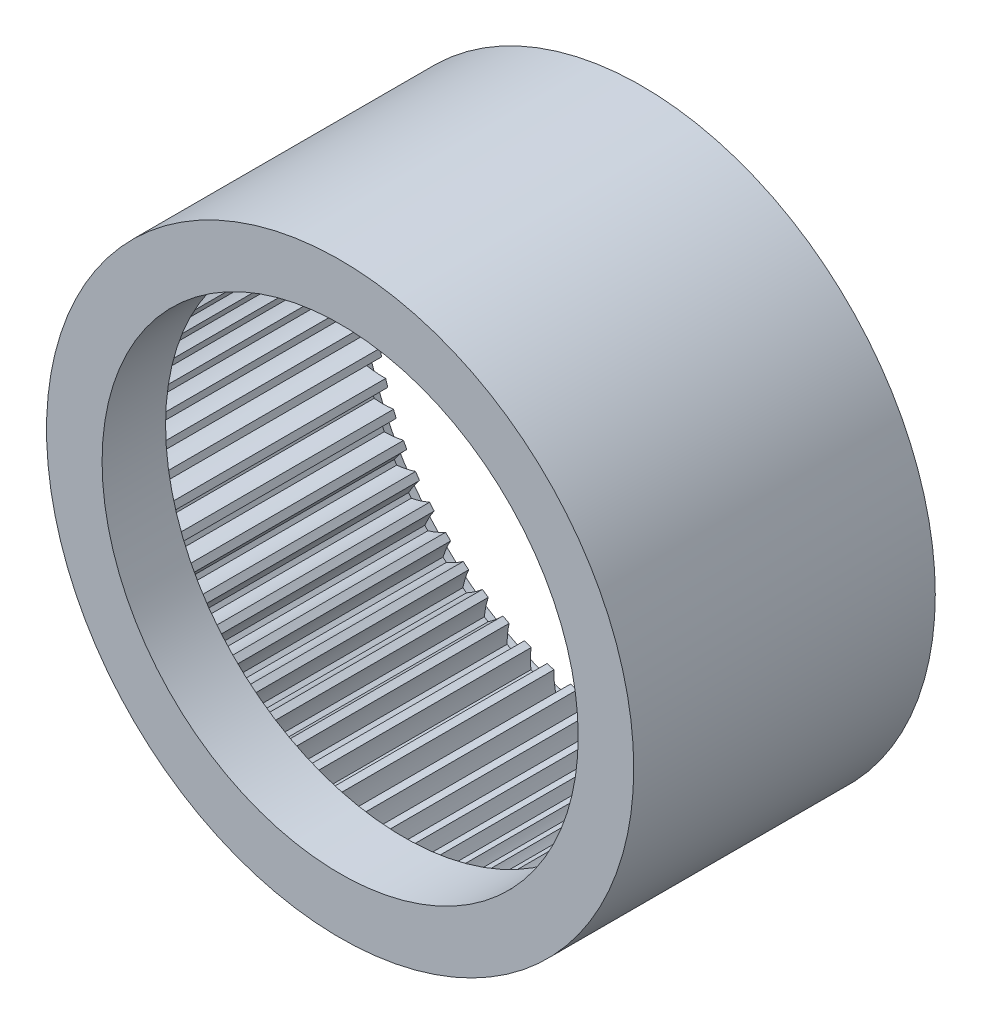
SolidWorks part; units mm, degrees
ref_plane "前视基准面" through (0, 0, 0) normal (0, 0, 1) x (1, 0, 0)
ref_plane "上视基准面" through (0, 0, 0) normal (0, 1, 0) x (1, 0, 0)
ref_plane "右视基准面" through (0, 0, 0) normal (1, 0, 0) x (0, 0, -1)
other "Configuration Table"
sketch "草图1" plane through (0, 0, 0) normal (0, 0, 1) x (1, 0, 0)
  circle A0 centre (0, 0) radius 33.25
  circle A1 centre (0, 0) radius 35.5
extrude "凸台-拉伸1" add sketch "草图1" along normal blind 30
ref_axis "基准轴1" through (0, 0, 30) along (0, 0, -1)
sketch "草图2" plane through (0, 0, 0) normal (0, 0, 1) x (1, 0, 0)
  line L0 (0, 0) -> (0, 31) construction
  arc A0 (0.4459, 30.9602) -> (-0.4459, 30.9602) centre (0, 0) ccw
  arc A1 (1.5868, 33.657) -> (-1.5868, 33.657) centre (0, 0) ccw
  spline S0 degree 3 poles (0.4459, 30.9602) (0.4728, 31.0632) (0.5181, 31.2226) (0.587, 31.441) (0.6477, 31.6208) (0.716, 31.8107) (0.7924, 32.0104) (0.8773, 32.2197) (0.9712, 32.4383) (1.0743, 32.666) (1.1872, 32.9024) (1.3547, 33.236) (1.4909, 33.4876) (1.5868, 33.657) knots 0 0 0 0 0.108783 0.16932 0.233953 0.302683 0.375509 0.452432 0.533452 0.618568 0.707781 0.801091 1 1 1 1
  spline S1 degree 3 poles (-0.4459, 30.9602) (-0.4728, 31.0632) (-0.5181, 31.2226) (-0.587, 31.441) (-0.6477, 31.6208) (-0.716, 31.8107) (-0.7924, 32.0104) (-0.8773, 32.2197) (-0.9712, 32.4383) (-1.0743, 32.666) (-1.1872, 32.9024) (-1.3547, 33.236) (-1.4909, 33.4876) (-1.5868, 33.657) knots 0 0 0 0 0.108783 0.16932 0.233953 0.302683 0.375509 0.452432 0.533452 0.618568 0.707781 0.801091 1 1 1 1
extrude "凸台-拉伸2" add sketch "草图2" along normal blind 30
pattern_circular "阵列(圆周)1" count 64 every 5.625 about axis through (0, 0, 30) along (0, 0, -1) of "凸台-拉伸2"
sketch "草图3" plane through (0, 0, 0) normal (0, 0, 1) x (1, 0, 0)
  circle A0 centre (0, 0) radius 32 construction
  dimension "Dn" = 64
sketch "草图4" plane through (0, 0, 30) normal (0, 0, 1) x (1, 0, 0)
  circle A0 centre (0, 0) radius 37
  dimension "D1" = 74
extrude "凸台-拉伸3" add sketch "草图4" along normal blind 8
sketch "草图5" plane through (0, 0, 30) normal (0, 0, -1) x (-1, 0, 0)
  circle A0 centre (0, 0) radius 35.5 construction
  circle A1 centre (0, 0) radius 37 construction
  circle A2 centre (0, 0) radius 35.5
  circle A3 centre (0, 0) radius 37
extrude "凸台-拉伸4" add sketch "草图5" along normal up to surface (30 mm away) up to face at (0, 0, 0)
sketch "草图6" plane through (0, 0, 0) normal (0, 0, -1) x (-1, 0, 0)
  circle A0 centre (0, 0) radius 35.5
  dimension "D1" = 71
extrude "切除-拉伸1" cut sketch "草图6" against normal blind 2.5
sketch "草图7" plane through (0, 0, 30) normal (0, 0, -1) x (-1, 0, 0)
  circle A0 centre (0, 0) radius 30
  dimension "D1" = 60
extrude "切除-拉伸2" cut sketch "草图7" against normal through all both and the other way through all
